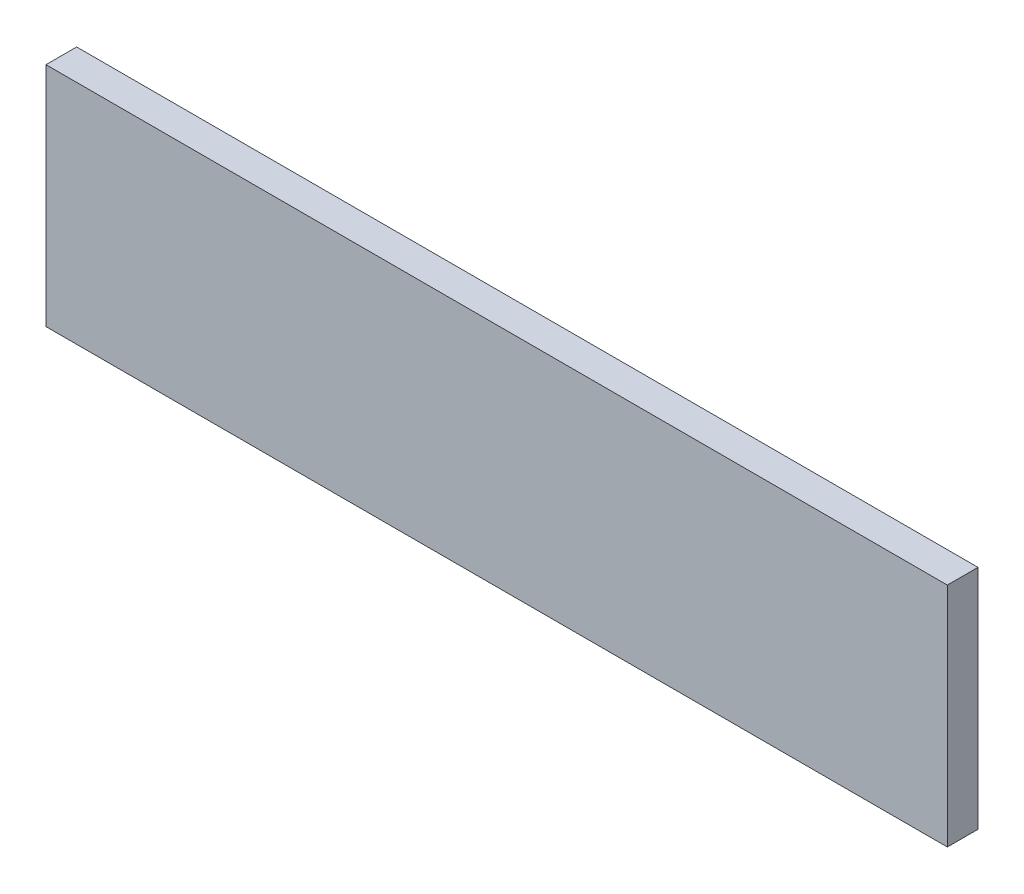
SolidWorks part; units mm, degrees
material "Plain Carbon Steel"
ref_plane "Front Plane" through (0, 0, 0) normal (0, 0, 1) x (1, 0, 0)
ref_plane "Top Plane" through (0, 0, 0) normal (0, 1, 0) x (1, 0, 0)
ref_plane "Right Plane" through (0, 0, 0) normal (1, 0, 0) x (0, 0, -1)
sketch "Sketch1" plane through (0, 0, 0) normal (0, 0, 1) x (1, 0, 0)
  line L1 (-330.3006, 99.1433) -> (-30.3006, 99.1433) construction
  line L2 (-330.3006, 99.1433) -> (-330.3006, 19.1433) construction
  line L3 (-330.3006, 19.1433) -> (-30.3006, 19.1433) construction
  line L4 (-30.3006, 99.1433) -> (-30.3006, 19.1433) construction
  line L8 (-327.3006, 96.1433) -> (-33.3006, 96.1433)
  line L9 (-33.3006, 96.1433) -> (-33.3006, 22.1433)
  line L10 (-327.3006, 22.1433) -> (-33.3006, 22.1433)
  line L11 (-327.3006, 96.1433) -> (-327.3006, 22.1433)
  line L13 (-30.3006, 99.1433) -> (-30.3006, 29.1433) construction
  line L14 (-30.3006, 99.1433) -> (-100.3006, 99.1433) construction
  line L15 (-30.3006, 19.1433) -> (-330.3006, 19.1433) construction
  line L16 (-330.3006, 99.1433) -> (-330.3006, 29.1433) construction
  dimension "D1" = 3
extrude "Boss-Extrude1" add sketch "Sketch1" along normal blind 10
sketch "Sketch3" plane through (0, 0, 0) normal (0, 0, -1) x (-1, 0, 0)
  line L0 (108.3006, 96.1433) -> (108.3006, 92.1433) construction
  line L1 (33.3006, 96.1433) -> (327.3006, 96.1433) construction
  line L2 (108.3006, 88.1433) -> (108.3006, 41.1433) construction
  line L3 (108.3006, 37.1433) -> (108.3006, 33.1433) construction
  line L5 (108.3006, 92.1433) -> (108.3006, 88.1433) construction
  line L6 (108.3006, 41.1433) -> (108.3006, 37.1433) construction
  line L7 (100.3006, 88.1433) -> (104.3006, 88.1433) construction
  line L8 (100.3006, 94.1433) -> (100.3006, 34.1433) construction
  line L9 (108.3006, 88.1433) -> (252.3006, 88.1433) construction
  line L10 (256.3006, 88.1433) -> (260.3006, 88.1433) construction
  line L11 (260.3006, 34.1433) -> (260.3006, 94.1433) construction
  line L12 (104.3006, 88.1433) -> (108.3006, 88.1433) construction
  line L13 (252.3006, 88.1433) -> (256.3006, 88.1433) construction
  line L14 (108.3006, 37.1433) -> (252.3006, 37.1433) construction
  line L15 (252.3006, 37.1433) -> (252.3006, 88.1433) construction
  line L16 (108.3006, 33.1433) -> (108.3006, 29.1433) construction
  circle A0 centre (108.3006, 88.1433) radius 4 construction
  dimension "D1" = 8
